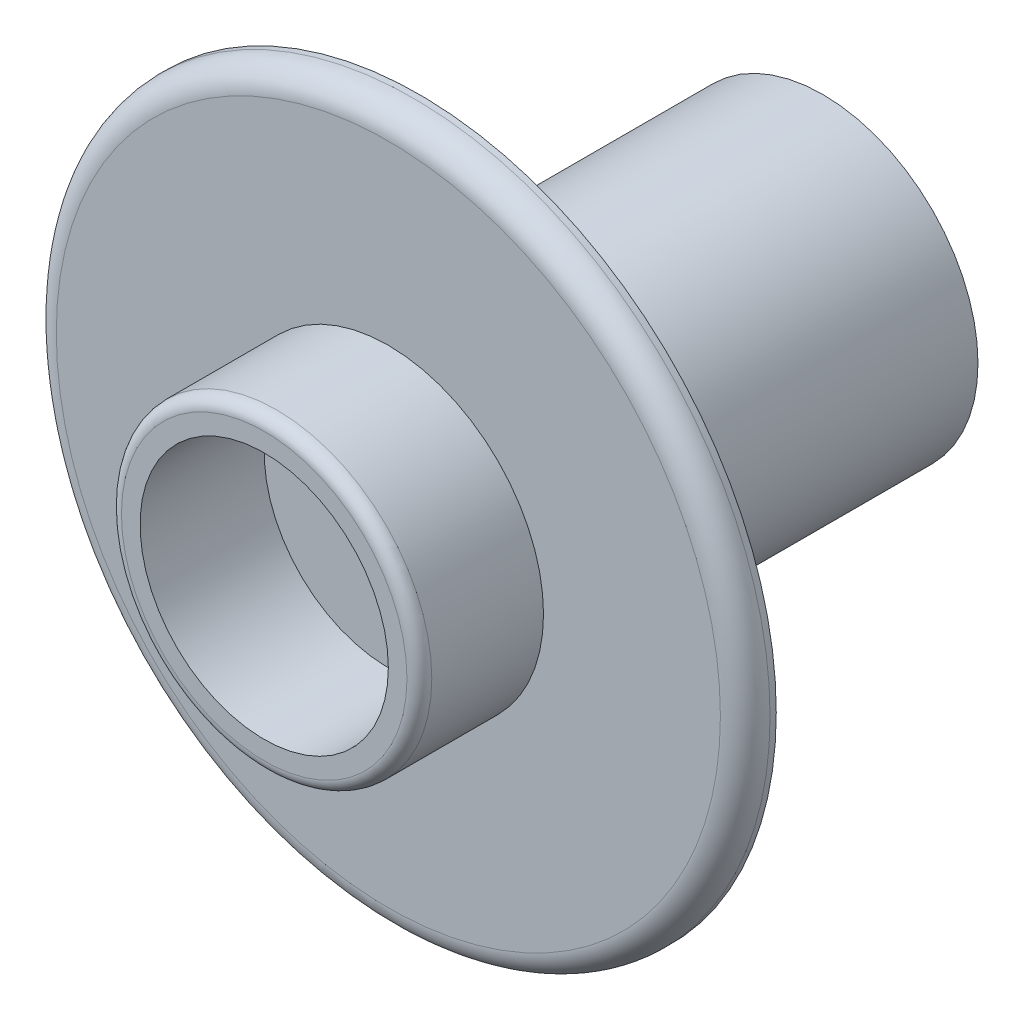
SolidWorks part; units mm, degrees
ref_plane "Front Plane" through (0, 0, 0) normal (0, 0, 1) x (1, 0, 0)
ref_plane "Top Plane" through (0, 0, 0) normal (0, 1, 0) x (1, 0, 0)
ref_plane "Right Plane" through (0, 0, 0) normal (1, 0, 0) x (0, 0, -1)
sketch "Sketch1" plane through (0, 0, 0) normal (0, 0, 1) x (1, 0, 0)
  circle A0 centre (0, 0) radius 36.5125
  dimension "D1" = 73.025
extrude "Boss-Extrude1" add sketch "Sketch1" along normal blind 3.175
sketch "Sketch2" plane through (0, 0, 0) normal (0, 0, -1) x (-1, 0, 0)
  circle A0 centre (0, 0) radius 15.875
  dimension "D1" = 31.75
extrude "Boss-Extrude2" add sketch "Sketch2" along normal blind 41.275
extrude "Boss-Extrude3" add sketch "Sketch2<2>" against normal blind 15.875
sketch "Sketch2<2>" plane through (0, 0, 0) normal (0, 0, -1) x (-1, 0, 0) same geometry as "Sketch2"
sketch "Sketch3" plane through (0, 0, 15.875) normal (0, 0, 1) x (1, 0, 0)
  circle A0 centre (0, 0) radius 12.7
  dimension "D1" = 25.4
extrude "Cut-Extrude1" cut sketch "Sketch3" against normal blind 12.7
fillet "Fillet1" radius 2.54 1 edges at (36.5125, 0, 3.175)
fillet "Fillet2" radius 1.27 1 edges at (-15.875, 0, 15.875)
